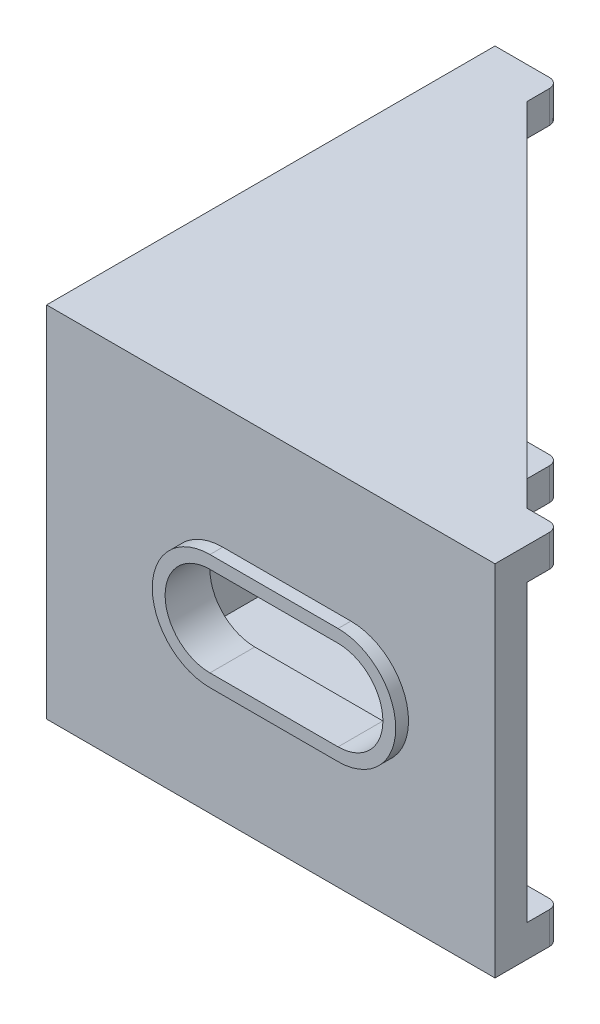
SolidWorks part; units mm, degrees
material "1060 Alloy"
ref_plane "Front Plane" through (0, 0, 0) normal (0, 0, 1) x (1, 0, 0)
ref_plane "Top Plane" through (0, 0, 0) normal (0, 1, 0) x (1, 0, 0)
ref_plane "Right Plane" through (0, 0, 0) normal (1, 0, 0) x (0, 0, -1)
sketch "Sketch1" plane through (0, 0, 0) normal (0, 1, 0) x (1, 0, 0)
  line L0 (0, 0) -> (0, 35)
  line L1 (0, 0) -> (35, 0)
  line L6 (2.5, 2.5) -> (35, 2.5)
  line L7 (2.5, 2.5) -> (2.5, 35)
  line L8 (0, 35) -> (2.5, 35)
  line L9 (35, 2.5) -> (35, 0)
  dimension "D2" = 35
  dimension "D3" = 35
  dimension "D1" = 2.5
extrude "Boss-Extrude1" add sketch "Sketch1" along normal blind 28
sketch "Sketch2" plane through (0, 28, 0) normal (0, 1, 0) x (1, 0, 0)
  line L0 (2.5, 35) -> (4.25, 35)
  line L1 (5, 34.25) -> (5, 32.5)
  line L2 (5, 32.5) -> (32.5, 5)
  line L3 (32.5, 5) -> (34.25, 5)
  line L4 (35, 4.25) -> (35, 2.5)
  line L5 (2.5, 2.5) -> (2.5, 35) construction
  line L6 (35, 2.5) -> (2.5, 2.5) construction
  line L7 (2.5, 2.5) -> (2.5, 35)
  line L8 (35, 2.5) -> (2.5, 2.5)
  arc A0 (34.25, 5) -> (35, 4.25) centre (34.25, 4.25) cw
  arc A1 (4.25, 35) -> (5, 34.25) centre (4.25, 34.25) cw
  point P12 (35, 5)
  dimension "D5" = 0.75
  dimension "D1" = 2.5
  dimension "D2" = 45
  dimension "D3" = 2.5
  dimension "D4" = 2.5
extrude "Boss-Extrude2" add sketch "Sketch2" against normal blind 2.5
extrude "Boss-Extrude3" add sketch "Sketch2<2>" along normal blind 2.5 from surface starting at face at (12.5, 0, -12.5)
sketch "Sketch2<2>" plane through (0, 28, 0) normal (0, 1, 0) x (1, 0, 0) same geometry as "Sketch2"
sketch "Sketch3" plane through (0, 0, -2.5) normal (0, 0, -1) x (-1, 0, 0)
  line L0 (-23.75, 14) -> (-13.75, 14) construction
  line L1 (-23.75, 17.5) -> (-13.75, 17.5)
  line L2 (-23.75, 10.5) -> (-13.75, 10.5)
  line L3 (-32.5, 25.5) -> (-5, 25.5) construction
  line L4 (-5, 2.5) -> (-32.5, 2.5) construction
  line L5 (-18.75, 2.5) -> (-18.75, 25.5) construction
  line L6 (-35, 2.5) -> (-2.5, 2.5) construction
  arc A0 (-23.75, 17.5) -> (-23.75, 10.5) centre (-23.75, 14) ccw
  arc A1 (-13.75, 10.5) -> (-13.75, 17.5) centre (-13.75, 14) ccw
  point P2 (-18.75, 14)
  dimension "D1" = 7
  dimension "D2" = 10
extrude "Cut-Extrude1" cut sketch "Sketch3" against normal blind 2.5
sketch "Sketch4" plane through (2.5, 0, 0) normal (1, 0, 0) x (0, 0, -1)
  line L0 (13.75, 14) -> (23.75, 14) construction
  line L1 (13.75, 17.5) -> (23.75, 17.5)
  line L2 (13.75, 10.5) -> (23.75, 10.5)
  line L3 (35, 25.5) -> (2.5, 25.5) construction
  line L4 (2.5, 2.5) -> (35, 2.5) construction
  line L5 (18.75, 2.5) -> (18.75, 25.5) construction
  line L6 (5, 25.5) -> (32.5, 25.5) construction
  arc A0 (13.75, 17.5) -> (13.75, 10.5) centre (13.75, 14) ccw
  arc A1 (23.75, 10.5) -> (23.75, 17.5) centre (23.75, 14) ccw
  point P2 (18.75, 14)
  dimension "D1" = 10
  dimension "D2" = 7
extrude "Cut-Extrude2" cut sketch "Sketch4" against normal blind 2.5
sketch "Sketch5" plane through (0, 0, 0) normal (0, 0, 1) x (1, 0, 0)
  line L0 (13.75, 17.5) -> (23.75, 17.5) construction
  line L1 (23.75, 10.5) -> (13.75, 10.5) construction
  line L2 (13.75, 17.5) -> (23.75, 17.5)
  line L3 (23.75, 10.5) -> (13.75, 10.5)
  line L4 (13.75, 18.5) -> (23.75, 18.5)
  line L5 (23.75, 9.5) -> (13.75, 9.5)
  arc A0 (13.75, 17.5) -> (13.75, 10.5) centre (13.75, 14) ccw construction
  arc A1 (23.75, 10.5) -> (23.75, 17.5) centre (23.75, 14) ccw construction
  arc A2 (13.75, 17.5) -> (13.75, 10.5) centre (13.75, 14) ccw
  arc A3 (23.75, 10.5) -> (23.75, 17.5) centre (23.75, 14) ccw
  arc A4 (23.75, 9.5) -> (23.75, 18.5) centre (23.75, 14) ccw
  arc A5 (13.75, 18.5) -> (13.75, 9.5) centre (13.75, 14) ccw
  dimension "D1" = 1
extrude "Boss-Extrude4" add sketch "Sketch5" along normal blind 1
sketch "Sketch6" plane through (0, 0, 0) normal (-1, 0, 0) x (0, 0, 1)
  line L0 (-13.75, 10.5) -> (-23.75, 10.5) construction
  line L1 (-23.75, 17.5) -> (-13.75, 17.5) construction
  line L2 (-13.75, 10.5) -> (-23.75, 10.5)
  line L3 (-23.75, 17.5) -> (-13.75, 17.5)
  line L4 (-23.75, 18.5) -> (-13.75, 18.5)
  line L5 (-13.75, 9.5) -> (-23.75, 9.5)
  arc A0 (-13.75, 10.5) -> (-13.75, 17.5) centre (-13.75, 14) ccw construction
  arc A1 (-13.75, 10.5) -> (-13.75, 17.5) centre (-13.75, 14) ccw
  arc A2 (-23.75, 17.5) -> (-23.75, 10.5) centre (-23.75, 14) ccw construction
  arc A3 (-23.75, 17.5) -> (-23.75, 10.5) centre (-23.75, 14) ccw
  arc A4 (-13.75, 9.5) -> (-13.75, 18.5) centre (-13.75, 14) ccw
  arc A5 (-23.75, 18.5) -> (-23.75, 9.5) centre (-23.75, 14) ccw
  dimension "D1" = 1
extrude "Boss-Extrude5" add sketch "Sketch6" along normal blind 1
